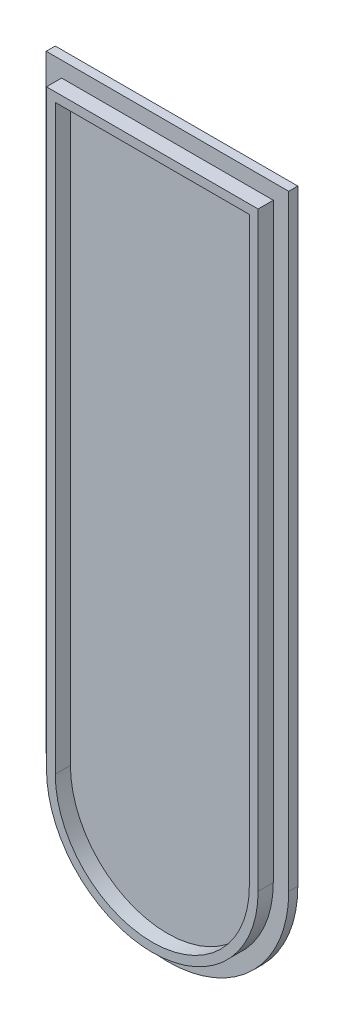
SolidWorks part; units mm, degrees
ref_plane "Plano frontal" through (0, 0, 0) normal (0, 0, 1) x (1, 0, 0)
ref_plane "Plano superior" through (0, 0, 0) normal (0, 1, 0) x (1, 0, 0)
ref_plane "Plano direito" through (0, 0, 0) normal (1, 0, 0) x (0, 0, -1)
sketch "Esboço1" plane through (0, 0, 0) normal (0, 0, 1) x (1, 0, 0)
  line L0 (-40, 0) -> (-40, 200)
  line L1 (-40, 200) -> (40, 200)
  line L2 (40, 200) -> (40, 0)
  arc A0 (-40, 0) -> (40, 0) centre (0, 0) ccw
  dimension "D1" = 80
  dimension "D2" = 200
extrude "Ressalto-extrusão1" add sketch "Esboço1" along normal blind 3
sketch "Esboço2" plane through (0, 0, 3) normal (0, 0, 1) x (1, 0, 0)
  line L0 (-34.9, 0) -> (-34.9, 194.9)
  line L1 (-34.9, 194.9) -> (34.9, 194.9)
  line L2 (34.9, 194.9) -> (34.9, 0)
  line L3 (40, 200) -> (-40, 200) construction
  line L4 (32, 0) -> (32, 191.9)
  line L5 (32, 191.9) -> (-32, 191.9)
  line L6 (-32, 191.9) -> (-32, 0)
  arc A0 (-34.9, 0) -> (34.9, 0) centre (0, 0) ccw
  arc A6 (-32, 0) -> (32, 0) centre (0, 0) ccw
  dimension "D1" = 69.8
  dimension "D3" = 64
  dimension "D2" = 5.1
  dimension "D4" = 3
extrude "Ressalto-extrusão2" add sketch "Esboço2" along normal blind 5
